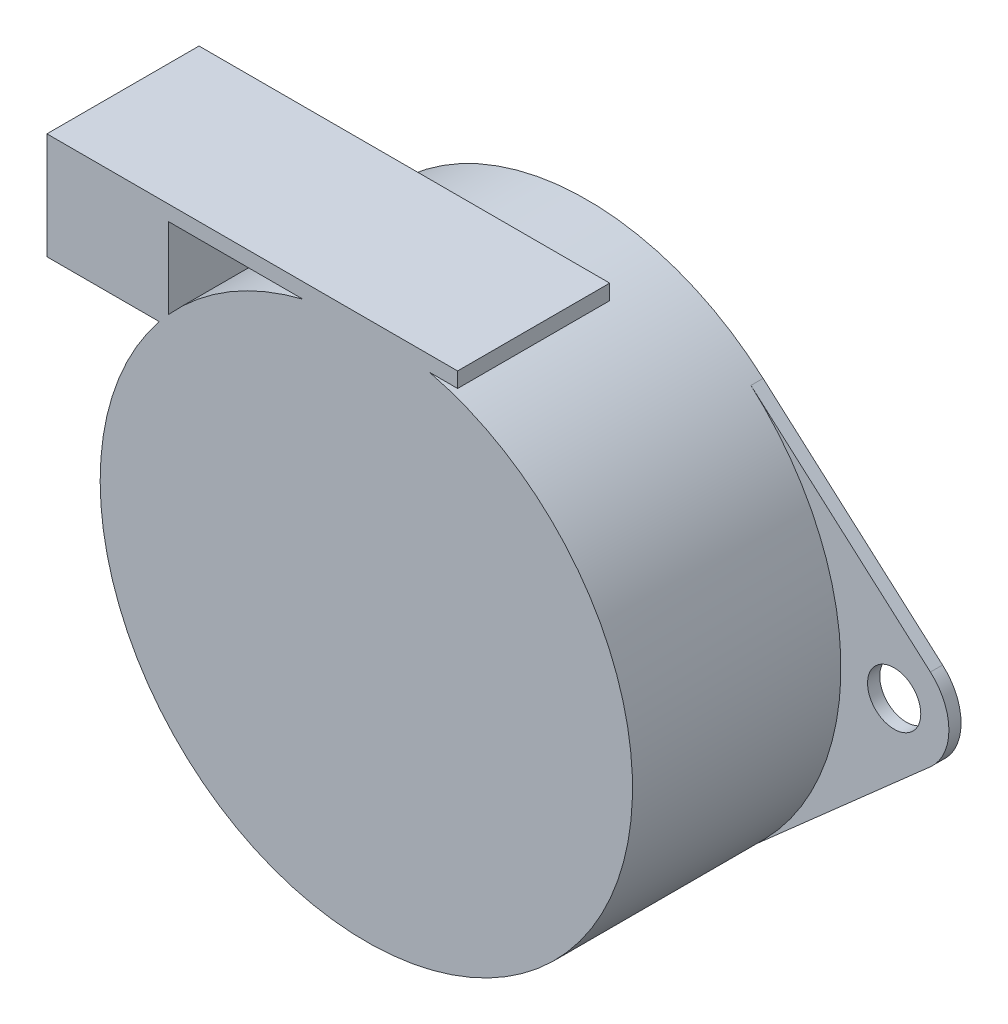
SolidWorks part; units mm, degrees
ref_plane "Спереди" through (0, 0, 0) normal (0, 0, 1) x (1, 0, 0)
ref_plane "Сверху" through (0, 0, 0) normal (0, 1, 0) x (1, 0, 0)
ref_plane "Справа" through (0, 0, 0) normal (1, 0, 0) x (0, 0, -1)
sketch "Эскиз1" plane through (0, 0, 0) normal (0, 0, 1) x (1, 0, 0)
  line L0 (0, 0) -> (-50000, 0) construction
  line L1 (-21, 6.0594) -> (-21, -49993.9406) construction
  line L2 (21, 9.9397) -> (21, -49990.0603) construction
  line L3 (0, 0) -> (0, 50000) construction
  line L4 (-35.809, -8.2741) -> (37443.5882, 33086.964) construction
  line L5 (-20.3144, -5.4081) -> (37459.0828, -33100.6462) construction
  line L6 (-11.5833, 13.1178) -> (-23.3829, 2.6985)
  line L7 (-23.3829, -2.6985) -> (-11.5833, -13.1178)
  line L8 (23.3829, -2.6985) -> (11.5833, -13.1178)
  line L9 (11.5833, 13.1178) -> (23.3829, 2.6985)
  circle A0 centre (0, 0) radius 17.5 construction
  circle A1 centre (-21, 0) radius 1.75
  arc A2 (-23.3829, 2.6985) -> (-23.3829, -2.6985) centre (-21, 0) ccw
  circle A3 centre (-21, 0) radius 3.6 construction
  arc A4 (-11.5833, -13.1178) -> (11.5833, -13.1178) centre (0, 0) ccw
  arc A5 (-11.5833, 13.1178) -> (11.5833, 13.1178) centre (0, 0) cw
  circle A6 centre (21, 0) radius 1.75
  arc A7 (23.3829, 2.6985) -> (23.3829, -2.6985) centre (21, 0) cw
  dimension "D3" = 21
extrude "Бобышка-Вытянуть1" add sketch "Эскиз1" along normal blind 0.8 contours A7 L9 A5 L6 A2 L7 A4 L8 A1 A6 region at (0, 0, 0)
sketch "Эскиз2" plane through (0, 0, 0.8) normal (0, 0, 1) x (1, 0, 0)
  circle A0 centre (0, 0) radius 17.5
extrude "Бобышка-Вытянуть2" add sketch "Эскиз2" along normal blind 13.7
sketch "Эскиз3" plane through (0, 0, 0) normal (0, 0, -1) x (-1, 0, 0)
  circle A0 centre (0, 0) radius 5
extrude "Бобышка-Вытянуть3" add sketch "Эскиз3" along normal blind 1.5
sketch "Эскиз4" plane through (0, 0, -1.5) normal (0, 0, -1) x (-1, 0, 0)
  circle A0 centre (0, 0) radius 1
extrude "Бобышка-Вытянуть4" add sketch "Эскиз4" along normal blind 6
sketch "Эскиз5" plane through (0, 0, 0) normal (0, 0, -1) x (-1, 0, 0)
  line L0 (21, 0) -> (-21, 0) construction
  line L1 (19.0967, 17.5) -> (-49980.9033, 17.5) construction
  arc A0 (11.5833, 13.1178) -> (-11.5833, 13.1178) centre (0, 0) ccw construction
ref_plane "Плоскость1" through (0, 17.5, 0) normal (0, 1, 0) x (1, 0, 0)
sketch "Эскиз6" plane through (0, 17.5, 0) normal (0, 1, 0) x (1, 0, 0)
  line L0 (0, 0) -> (0, -50000) construction
  line L1 (-24.1111, -14.5) -> (49975.8889, -14.5) construction
  line L2 (-17.5, -14.5) -> (17.5, -14.5) construction
  line L3 (-23.4024, -4.5) -> (49976.5976, -4.5) construction
  line L4 (6, 6.4815) -> (6, -49993.5185) construction
  line L5 (-21, 11.7061) -> (-21, -49988.2939) construction
  line L7 (-21, -4.5) -> (6, -4.5)
  line L8 (-21, -4.5) -> (-21, -14.5)
  line L9 (-21, -14.5) -> (6, -14.5)
  line L10 (6, -4.5) -> (6, -14.5)
  dimension "D1" = 10
  dimension "D2" = 6
  dimension "D3" = 21
extrude "Бобышка-Вытянуть5" add sketch "Эскиз6" along normal blind 0.5 and the other way blind 0.5 separate body
sketch "Эскиз7" plane through (0, 17, 0) normal (0, -1, 0) x (1, 0, 0)
  line L0 (-21, 14.5) -> (6, 14.5) construction
  line L1 (-21, 4.5) -> (-13, 4.5)
  line L2 (-21, 4.5) -> (-21, 14.5)
  line L3 (-21, 14.5) -> (-13, 14.5)
  line L4 (-13, 4.5) -> (-13, 14.5)
  dimension "D1" = 8
extrude "Бобышка-Вытянуть6" add sketch "Эскиз7" along normal blind 6
